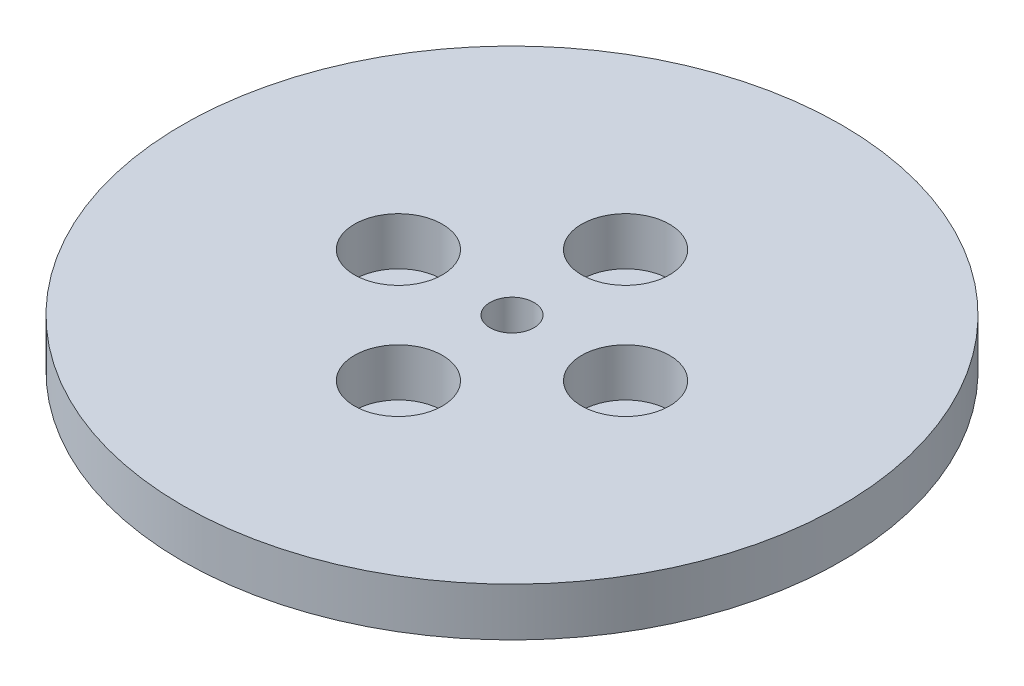
SolidWorks part; units mm, degrees
ref_plane "Front Plane" through (0, 0, 0) normal (0, 0, 1) x (1, 0, 0)
ref_plane "Top Plane" through (0, 0, 0) normal (0, 1, 0) x (1, 0, 0)
ref_plane "Right Plane" through (0, 0, 0) normal (1, 0, 0) x (0, 0, -1)
sketch "Sketch1" plane through (0, 0, 0) normal (0, 1, 0) x (1, 0, 0)
  circle A0 centre (0, 0) radius 75
  dimension "FLANGE_OD" = 150
extrude "Boss-Extrude1" add sketch "Sketch1" along normal blind 11
sketch "Sketch2" plane through (0, 0, 0) normal (0, 1, 0) x (1, 0, 0)
  circle A0 centre (0, 0) radius 5
  dimension "BORE_D" = 10
extrude "Cut-Extrude1" cut sketch "Sketch2" along normal through all
sketch "Sketch3" plane through (0, 11, 0) normal (0, 1, 0) x (1, 0, 0)
  circle A0 centre (0, 0) radius 25.8487 construction
  circle A1 centre (-25.8487, 0) radius 10
  dimension "BOLT_D" = 20
  dimension "BOLT_PCD" = 51.6974
extrude "Cut-Extrude2" cut sketch "Sketch3" against normal blind 10.8732
pattern_circular "CirPattern1" count 4 over 360 about axis through (0, 0, 0) along (0, 1, 0) of "Cut-Extrude2"
